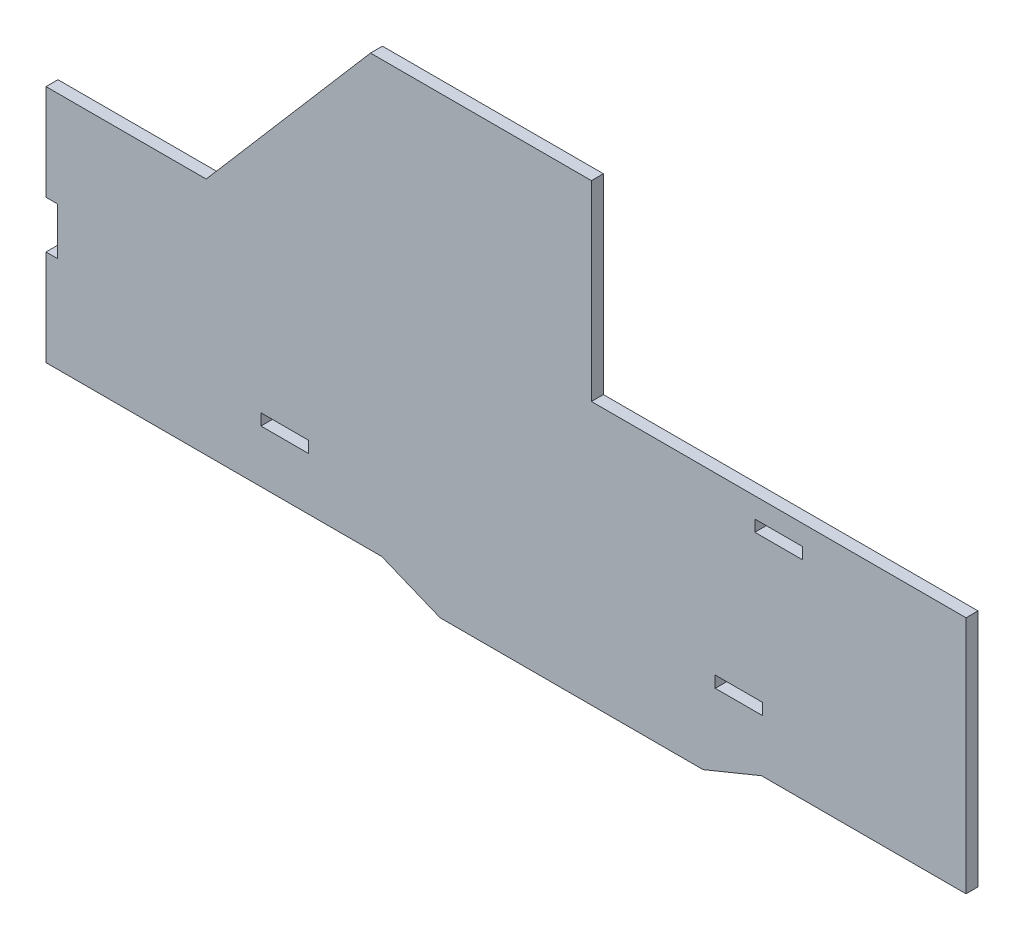
SolidWorks part; units mm, degrees
ref_plane "Front Plane" through (0, 0, 0) normal (0, 0, 1) x (1, 0, 0)
ref_plane "Top Plane" through (0, 0, 0) normal (0, 1, 0) x (1, 0, 0)
ref_plane "Right Plane" through (0, 0, 0) normal (1, 0, 0) x (0, 0, -1)
sketch "Sketch1" plane through (0, 0, 0) normal (0, 0, 1) x (1, 0, 0)
  line L0 (62.1239, 6.35) -> (131.9663, 6.35)
  line L1 (201.8088, 12.7) -> (201.8088, 76.2)
  line L2 (201.8088, 76.2) -> (102.3141, 76.2)
  line L3 (102.3141, 76.2) -> (102.3141, 127)
  line L4 (102.3141, 127) -> (43.6394, 127)
  line L5 (43.6394, 127) -> (0, 76.2)
  line L6 (0, 76.2) -> (-42.5392, 76.2)
  line L7 (-42.5392, 76.2) -> (-42.5392, 12.7)
  line L9 (-42.5392, 12.7) -> (46.6174, 12.7)
  line L10 (46.6174, 12.7) -> (62.1239, 6.35)
  line L11 (201.8088, 12.7) -> (147.4729, 12.7)
  line L12 (147.4729, 12.7) -> (131.9663, 6.35)
  dimension "D1" = 244.348
  dimension "D2" = 6.35
  dimension "D3" = 50.8
  dimension "D4" = 63.5
  dimension "D5" = 99.4947
  dimension "D6" = 16.7564
  dimension "D7" = 16.7564
extrude "Main Side" add sketch "Sketch1" along normal blind 3.175
sketch "Sketch2" plane through (0, 0, 3.175) normal (0, 0, 1) x (1, 0, 0)
  line L0 (-39.4912, 76.2) -> (-39.4912, 12.7) construction
  line L15 (0, 76.2) -> (-42.5392, 76.2) construction
  line L16 (-42.5392, 76.2) -> (-42.5392, 12.7) construction
  line L26 (-39.4912, 18.5744) -> (201.8088, 18.5744) construction
  line L27 (201.8088, 12.7) -> (201.8088, 76.2) construction
  line L28 (81.1588, 18.5744) -> (81.1588, 127) construction
  line L29 (102.3141, 127) -> (43.6394, 127) construction
  line L30 (81.1588, 36.7006) -> (201.8088, 36.7006) construction
  line L41 (62.1239, 6.35) -> (131.9663, 6.35) construction
  line L42 (135.1973, 29.718) -> (147.7703, 29.718)
  line L43 (135.1973, 29.718) -> (135.1973, 26.67)
  line L44 (135.1973, 26.67) -> (147.7703, 26.67)
  line L45 (147.7703, 29.718) -> (147.7703, 26.67)
  line L46 (14.5473, 29.718) -> (14.5473, 26.67)
  line L47 (27.1203, 26.67) -> (14.5473, 26.67)
  line L48 (27.1203, 29.718) -> (27.1203, 26.67)
  line L49 (27.1203, 29.718) -> (14.5473, 29.718)
  line L51 (-42.5392, 12.7) -> (46.6174, 12.7) construction
  point P20 (141.4838, 29.718)
  point P21 (141.4838, 36.7006)
  dimension "D1" = 12.573
  dimension "D2" = 3.048
  dimension "D3" = 20.32
  dimension "D4" = 3.048
extrude "Bottom Plate Holes" cut sketch "Sketch2" against normal through all
sketch "Sketch3" plane through (0, 0, 3.175) normal (0, 0, 1) x (1, 0, 0)
  line L1 (145.7115, 70.866) -> (158.4115, 70.866)
  line L2 (145.7115, 70.866) -> (145.7115, 67.818)
  line L3 (145.7115, 67.818) -> (158.4115, 67.818)
  line L4 (158.4115, 70.866) -> (158.4115, 67.818)
  line L6 (147.7703, 29.718) -> (135.1973, 29.718) construction
  line L7 (201.8088, 76.2) -> (102.3141, 76.2) construction
  point P8 (152.0615, 76.2)
  point P9 (152.0615, 70.866)
  dimension "D1" = 12.7
  dimension "D2" = 3.048
  dimension "D3" = 38.1
extrude "Cut-Extrude1" cut sketch "Sketch3" against normal through all
sketch "Sketch4" plane through (0, 0, 3.175) normal (0, 0, 1) x (1, 0, 0)
  line L0 (-42.5392, 76.2) -> (-42.5392, 12.7) construction
  line L1 (-42.5392, 50.7365) -> (-39.4912, 50.7365)
  line L2 (-42.5392, 50.7365) -> (-42.5392, 38.1635)
  line L3 (-42.5392, 38.1635) -> (-39.4912, 38.1635)
  line L4 (-39.4912, 50.7365) -> (-39.4912, 38.1635)
  point P6 (-42.5392, 44.45)
  point P7 (-42.5392, 44.45)
  dimension "D1" = 3.048
  dimension "D2" = 12.573
extrude "Cut-Extrude2" cut sketch "Sketch4" against normal through all
